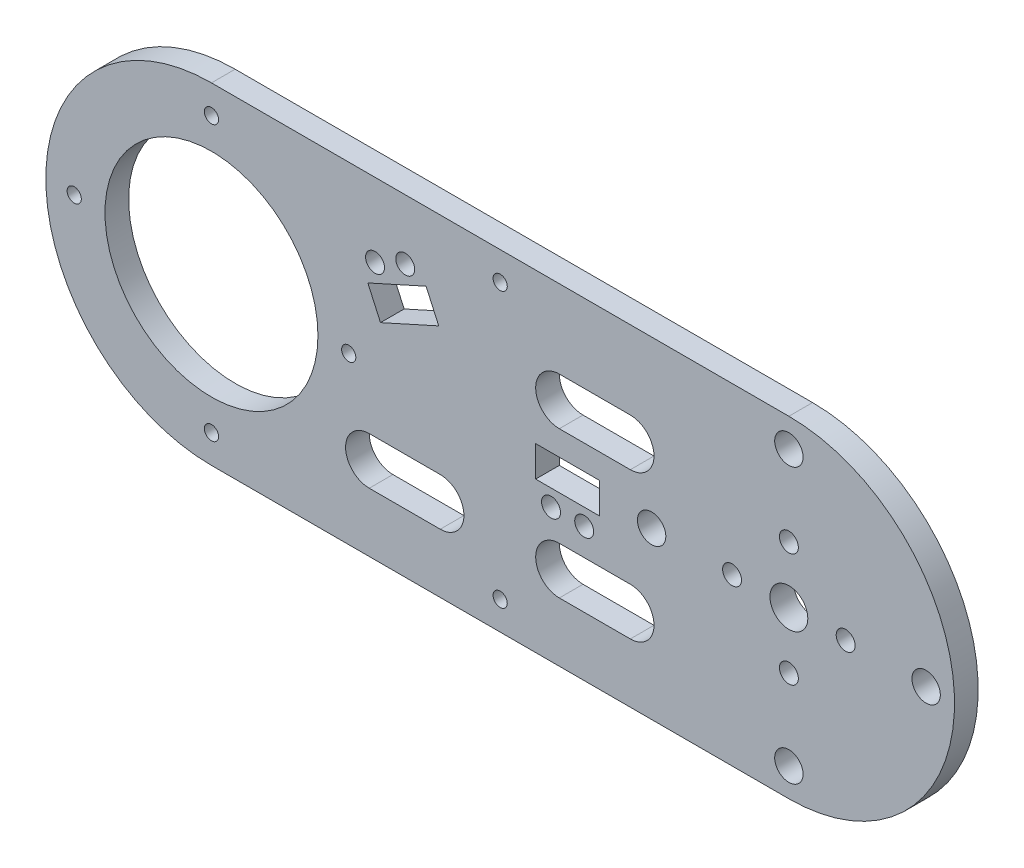
SolidWorks part; units mm, degrees
ref_plane "Front Plane" through (0, 0, 0) normal (0, 0, 1) x (1, 0, 0)
ref_plane "Top Plane" through (0, 0, 0) normal (0, 1, 0) x (1, 0, 0)
ref_plane "Right Plane" through (0, 0, 0) normal (1, 0, 0) x (0, 0, -1)
sketch "Sketch1" plane through (0, 0, 0) normal (0, 0, 1) x (1, 0, 0)
  line L0 (61, 0) -> (-61, 0) construction
  line L1 (12.5, -17.5) -> (12.5, 13.47) construction
  line L2 (61, -35) -> (-61, -35)
  line L3 (61, 35) -> (-61, 35)
  line L17 (7.5, 3.25) -> (7.5, -3.25)
  line L20 (7.5, -3.25) -> (21, -3.25)
  line L23 (21, -3.25) -> (21, 3.25)
  line L24 (21, 3.25) -> (7.5, 3.25)
  line L27 (-27.66, -17.5) -> (-12.66, -17.5) construction
  line L28 (12.5, -17.5) -> (27.5, -17.5) construction
  line L29 (-27.66, -12.5) -> (-12.66, -12.5)
  line L30 (-27.66, -22.5) -> (-12.66, -22.5)
  line L31 (12.5, 13.47) -> (27.5, 13.47) construction
  line L32 (12.5, -12.5) -> (27.5, -12.5)
  line L33 (12.5, -22.5) -> (27.5, -22.5)
  line L35 (12.5, 18.47) -> (27.5, 18.47)
  line L36 (12.5, 8.47) -> (27.5, 8.47)
  line L37 (-61, 0) -> (-27.959, 14.9116) construction
  line L38 (-27.959, 14.9116) -> (-25.2852, 8.987)
  line L39 (-25.2852, 8.987) -> (-12.9803, 14.5403)
  line L40 (-12.9803, 14.5403) -> (-15.6541, 20.4649)
  line L41 (-15.6541, 20.4649) -> (-27.959, 14.9116)
  arc A0 (61, -35) -> (61, 35) centre (61, 0) ccw
  arc A1 (-61, 35) -> (-61, -35) centre (-61, 0) ccw
  circle A2 centre (61, 0) radius 4
  circle A3 centre (-61, 0) radius 22.5
  circle A4 centre (-61, -29) radius 1.5
  circle A5 centre (-61, 29) radius 1.5
  circle A6 centre (61, 29) radius 3
  circle A7 centre (61, -29) radius 3
  circle A8 centre (0, -29) radius 1.5
  circle A9 centre (0, 29) radius 1.5
  circle A12 centre (-90, 0) radius 1.5
  circle A13 centre (-32, 0) radius 1.5
  circle A16 centre (90, 0) radius 3
  circle A17 centre (32, 0) radius 3
  circle A34 centre (61, 12) radius 2
  circle A35 centre (61, -12) radius 2
  circle A36 centre (49, 0) radius 2
  circle A37 centre (73, 0) radius 2
  arc A38 (-27.66, -12.5) -> (-27.66, -22.5) centre (-27.66, -17.5) ccw
  arc A39 (-12.66, -22.5) -> (-12.66, -12.5) centre (-12.66, -17.5) ccw
  arc A40 (12.5, -12.5) -> (12.5, -22.5) centre (12.5, -17.5) ccw
  arc A41 (27.5, -22.5) -> (27.5, -12.5) centre (27.5, -17.5) ccw
  arc A42 (12.5, 18.47) -> (12.5, 8.47) centre (12.5, 13.47) ccw
  arc A43 (27.5, 8.47) -> (27.5, 18.47) centre (27.5, 13.47) ccw
  circle A44 centre (10.75, -6.75) radius 2
  circle A45 centre (17.75, -6.75) radius 2
  circle A46 centre (-20.0562, 22.3182) radius 2
  circle A47 centre (-26.4365, 19.4387) radius 2
  point P5 (0, 0)
  point P27 (-61, 0)
  point P28 (7.5, 0)
  point P32 (-61, 0)
  point P53 (-20.16, -17.5)
  point P59 (20, -17.5)
  point P66 (20, 13.47)
  point P74 (14.25, -6.75)
  point P83 (-23.2463, 20.8784)
  dimension "D1" = 8
  dimension "D3" = 6
  dimension "D4" = 3
  dimension "D5" = 6
  dimension "D6" = 3
  dimension "D8" = 6
  dimension "D9" = 6
  dimension "D12" = 3
  dimension "D13" = 3
  dimension "D14" = 70
  dimension "D15" = 12
  dimension "D16" = 12
  dimension "D19" = 3
  dimension "D20" = 3
  dimension "D24" = 29
  dimension "D25" = 6
  dimension "D26" = 6
  dimension "D27" = 4
  dimension "D28" = 4
  dimension "D29" = 4
  dimension "D30" = 29
  dimension "D31" = 13.5
  dimension "D32" = 6.5
  dimension "D33" = 68.5
  dimension "D34" = 33.34
  dimension "D45" = 45
  dimension "D22" = 4
  dimension "D41" = 4
  dimension "D42" = 4
  dimension "D46" = 6
  dimension "D48" = 13.5
  dimension "D7" = 122
  dimension "D10" = 6
  dimension "D11" = 6
  dimension "D17" = 12
  dimension "D18" = 58
  dimension "D21" = 12
  dimension "D23" = 29
  dimension "D35" = 15
  dimension "D36" = 10
  dimension "D37" = 73.5
  dimension "D38" = 15
  dimension "D39" = 10
  dimension "D40" = 30.97
  dimension "D43" = 7
  dimension "D44" = 36.25
  dimension "D47" = 6
  dimension "D49" = 6.5
  dimension "D50" = 7
  dimension "D51" = 3.5
extrude "Boss-Extrude1" add sketch "Sketch1" along normal blind 5
